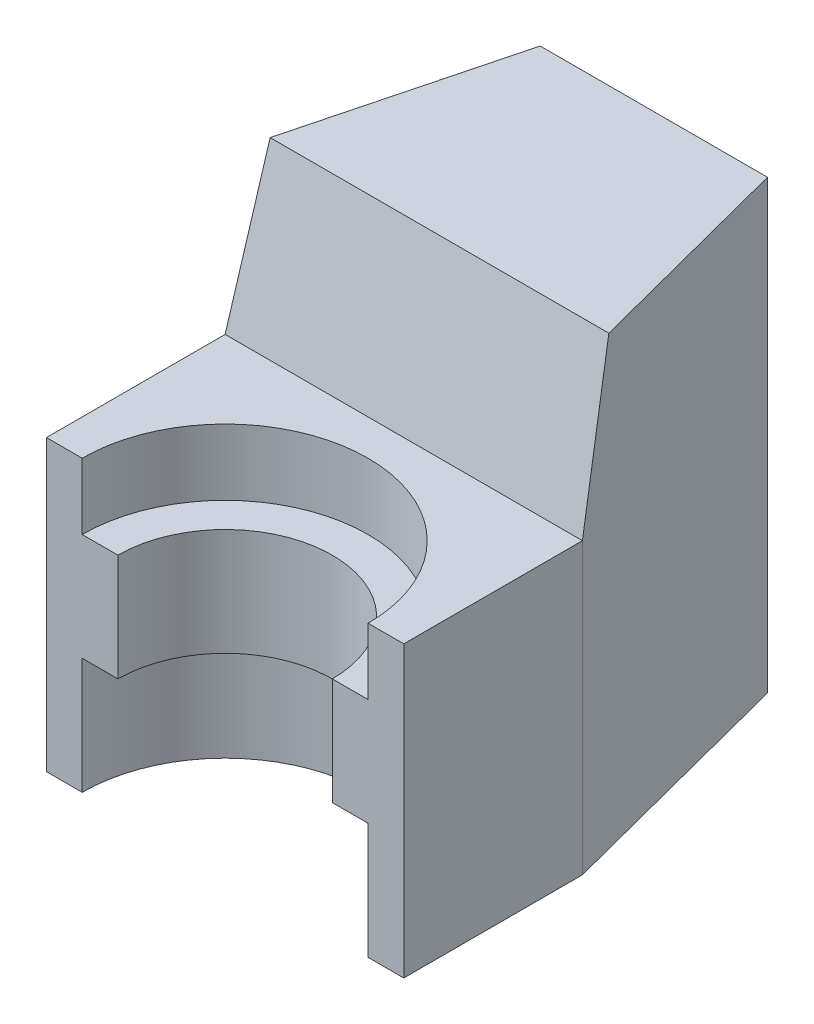
SolidWorks part; units mm, degrees
material "PLA"
ref_plane "Front Plane" through (0, 0, 0) normal (0, 0, 1) x (1, 0, 0)
ref_plane "Top Plane" through (0, 0, 0) normal (0, 1, 0) x (1, 0, 0)
ref_plane "Right Plane" through (0, 0, 0) normal (1, 0, 0) x (0, 0, -1)
sketch "Sketch1" plane through (0, 0, 0) normal (1, 0, 0) x (0, 0, -1)
  line L0 (0, 20) -> (12, 20) construction
  line L1 (0, 0) -> (12, 0)
  line L2 (0, 0) -> (0, 25)
  line L3 (0, 25) -> (12, 25)
  line L4 (12, 0) -> (12, 25)
  line L5 (0, 5) -> (12, 5) construction
  dimension "D1" = 15
  dimension "D2" = 12
  dimension "D3" = 25
  dimension "D4" = 5
extrude "Boss-Extrude1" add sketch "Sketch1" along normal mid plane 20 contours L4 L3 L2 L1
sketch "Sketch2" plane through (0, 0, 0) normal (0, 1, 0) x (1, 0, 0)
  line L0 (0, 0) -> (0, -2) construction
  line L1 (-10, -12) -> (10, -12)
  line L2 (-10, -12) -> (-10, -2)
  line L3 (-10, -2) -> (10, -2)
  line L4 (10, -12) -> (10, -2)
  dimension "D1" = 2
  dimension "D2" = 20
  dimension "D3" = 10
extrude "Boss-Extrude2" add sketch "Sketch2" along normal blind 16.2 separate body
sketch "Sketch3" plane through (10, 0, 0) normal (1, 0, 0) x (0, 0, -1)
  line L1 (-2, 0) -> (-2, 16.2) construction
  line L7 (0, 25) -> (0, 0) construction
  line L9 (-2, 0) -> (-2, 16.2)
  line L15 (0, 25) -> (0, 0)
  line L16 (0, 25) -> (-2, 16.2)
  line L17 (-2, 0) -> (0, 0)
extrude "Boss-Extrude3" add sketch "Sketch3" against normal up to surface (20 mm away) up to face at (-10, 8.1, 7)
hole_wizard "M5x0.8 Tapped Hole1" positions "Sketch7" profile "Sketch6" tap size "M5x0.8" standard "ANSI Metric"
sketch "Sketch7" plane through (0, 0, -12) normal (0, 0, -1) x (-1, 0, 0)
  line L0 (-10, 0) -> (10, 0) construction
  point P0 (0, 20)
  point P2 (0, 5)
  dimension "D1" = 15
  dimension "D2" = 5
sketch "Sketch6" plane through (0, 20, -12) normal (1, 0, 0) x (0, 1, 0)
  line L0 (0, 0) -> (0, 8.2618)
  line L1 (0, 8.2618) -> (2.1, 7)
  line L2 (2.1, 7) -> (2.1, 0)
  line L5 (2.1, 0) -> (0, 0)
  line L10 (0, 8.2618) -> (-2.1, 7) construction
  line L11 (0, -6.35) -> (0, 107.95) construction
  dimension "Tap Drill Dia." = 4.2
  dimension "Tap Drill Depth" = 7
  dimension "Drill Angle" = 118
cosmetic thread "Hole Thread1" parameters "D1"=4.2, "D2"=5
cosmetic thread "Hole Thread2" parameters "D1"=4.2, "D2"=5
sketch "Sketch9" plane through (0, 0, 0) normal (1, 0, 0) x (0, 0, -1)
  line L0 (-12, 16.2) -> (-4, 16.2)
  line L1 (-12, 16.2) -> (-12, 0) construction
  line L2 (-4, 16.2) -> (-4, 12.5)
  line L3 (-4, 12.5) -> (-6, 12.5)
  line L4 (-6, 12.5) -> (-6, 6.5)
  line L5 (-6, 6.5) -> (-4, 6.5)
  line L6 (-4, 6.5) -> (-4, 0)
  line L7 (-12, 0) -> (12, 0) construction
  line L8 (-4, 0) -> (-12, 0)
  line L9 (-12, 0) -> (-12, 16.2)
  line L10 (-12, 16.2) -> (-2, 16.2) construction
  dimension "D1" = 6
  dimension "D2" = 8
  dimension "D3" = 8
  dimension "D4" = 6.5
  dimension "D5" = 6
revolve "Cut-Revolve1" cut sketch "Sketch9" angle 360 about L9
sketch "Sketch10" plane through (0, 25, 0) normal (0, 1, 0) x (1, 0, 0)
  line L5 (10, -2) -> (10, 0) construction
  line L6 (-10, -2) -> (-6.3625, 12)
  line L7 (10, 12) -> (-10, 12) construction
  line L8 (-6.3625, 12) -> (-10, 12)
  line L9 (-10, 12) -> (-10, -2)
  line L10 (10, 12) -> (6.3625, 12)
  line L11 (10, -2) -> (10, 0)
  line L12 (6.3625, 12) -> (10, -2)
  line L13 (10, 12) -> (10, -2)
  line L14 (0, 0) -> (0, 12) construction
  line L15 (10, 0) -> (-10, 0) construction
  line M4 (-10, 12) -> (-10, 0)
  line M5 (-10, 0) -> (10, 0)
  line M6 (10, 0) -> (10, 12)
  line M7 (10, 12) -> (-10, 12)
  dimension "D1" = 12.725
extrude "Cut-Extrude2" cut sketch "Sketch10" against normal up to next contours L12 M7 M5 M6 | L12 L11 M5 | L6 M5 M7 M4 | L9 L6 M5 region at (-9.8268, 25, 0.6667) region at (-8.7658, 25, -7.5) region at (9.8268, 25, 0.6667) region at (8.7658, 25, -7.5)
